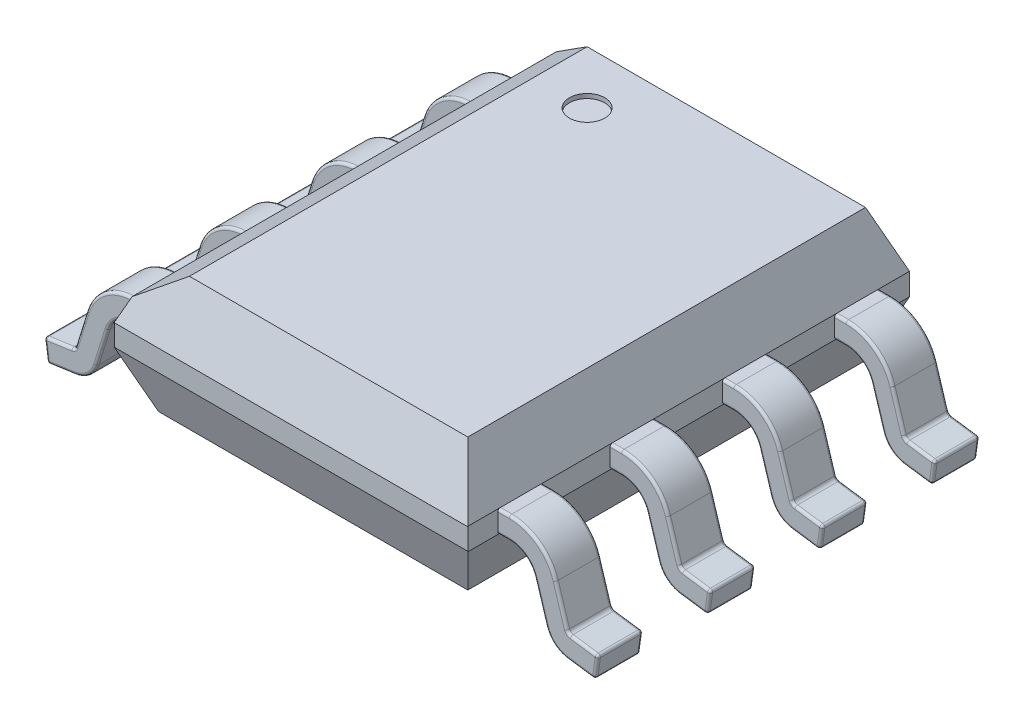
SolidWorks part; units mm, degrees
ref_plane "Front" through (0, 0, 0) normal (0, 0, 1) x (1, 0, 0)
ref_plane "Top" through (0, 0, 0) normal (0, 1, 0) x (1, 0, 0)
ref_plane "Right" through (0, 0, 0) normal (1, 0, 0) x (0, 0, -1)
sketch "Эскиз1" plane through (0, 0, 0) normal (0, 0, 1) x (1, 0, 0)
  line L0 (-1.75, 0.25) -> (1.75, 0.25)
  line L1 (1.75, 0.25) -> (2, 0.875)
  line L2 (2, 0.875) -> (2, 1.125)
  line L3 (2, 1.125) -> (1.75, 1.75)
  line L4 (1.75, 1.75) -> (-1.4, 1.75)
  line L5 (-1.4, 1.75) -> (-1.9, 1.375)
  line L6 (-1.9, 1.375) -> (-2, 1.125)
  line L7 (-2, 1.125) -> (-2, 0.875)
  line L8 (-2, 0.875) -> (-1.75, 0.25)
  line L9 (0, 0.25) -> (0, 1.75) construction
  line L10 (-2, 0.875) -> (-2.1291, 0.875)
  line L11 (-2.4155, 0.664) -> (-2.5436, 0.2519)
  line L12 (-2.7883, 0.0438) -> (-3.1, 0)
  line L13 (-2, 1.125) -> (-2.1291, 1.125)
  line L14 (-2.6543, 0.7382) -> (-2.7823, 0.3261)
  line L15 (-2.8231, 0.2914) -> (-3.1348, 0.2476)
  line L16 (-3.1, 0) -> (-3.1348, 0.2476)
  line L17 (-3.1, 0) -> (0, 0) construction
  line L18 (-2, 1) -> (2, 1) construction
  arc A0 (-2.7883, 0.0438) -> (-2.5436, 0.2519) centre (-2.8301, 0.3409) ccw
  arc A1 (-2.4155, 0.664) -> (-2.1291, 0.875) centre (-2.1291, 0.575) cw
  arc A2 (-2.6543, 0.7382) -> (-2.1291, 1.125) centre (-2.1291, 0.575) cw
  arc A3 (-2.8231, 0.2914) -> (-2.7823, 0.3261) centre (-2.8301, 0.3409) ccw
  point P11 (0, 1)
  point P18 (-2.6, 0.0703)
  point P24 (-2.35, 0.875)
  dimension "D11" = 0.3
  dimension "D1" = 1.5
  dimension "D2" = 0.25
  dimension "D3" = 4
  dimension "D4" = 0.25
  dimension "D5" = 0.25
  dimension "D6" = 0.5
  dimension "D7" = 0.25
  dimension "D8" = 3.1
  dimension "D9" = 8
  dimension "D10" = 0.5
  dimension "D12" = 0.25
  dimension "D13" = 0.25
  dimension "D14" = 0.625
extrude "Бобышка-Вытянуть1" add sketch "Эскиз1" along normal blind 2.5 and the other way blind 2.5 contours L7 L8 L0 L1 L2 L3 L4 L5 L6 region at (0.0196, 0.9927, 0)
extrude "Бобышка-Вытянуть2" add sketch "Эскиз1<3>" along normal blind 0.255 and the other way blind 0.255 from offset 1.905 separate body contours A3 L15 L16 L12 A0 L11 A1 L10 L7 L13 A2 L14 region at (-2.5637, 0.567, 0)
sketch "Эскиз1<3>" plane through (0, 0, 0) normal (0, 0, 1) x (1, 0, 0) same geometry as "Эскиз1"
fillet "Скругление1" radius 0.03 24 edges at (-2.0645, 0.875, 1.65) (-2.307, 0.8166, 1.65) (-2.4796, 0.4579, 1.65) (-2.6358, 0.1123, 1.65) (-2.0645, 0.875, 2.16) (-2.307, 0.8166, 2.16) (-2.4796, 0.4579, 2.16) (-2.6358, 0.1123, 2.16) (-2.7183, 0.5321, 1.65) (-2.0645, 1.125, 1.65) (-2.7183, 0.5321, 2.16) (-2.0645, 1.125, 2.16) (-3.1174, 0.1238, 1.65) (-3.1, 0, 1.905) (-3.1174, 0.1238, 2.16) (-3.1348, 0.2476, 1.905) (-2.9442, 0.0219, 1.65) (-2.979, 0.2695, 1.65) (-2.979, 0.2695, 2.16) (-2.9442, 0.0219, 2.16) (-2.7977, 0.3028, 1.65) (-2.4552, 1.0179, 1.65) (-2.7977, 0.3028, 2.16) (-2.4552, 1.0179, 2.16)
pattern_linear "Линейный массив1" count 4 spacing 1.27 along (0, 0, -1) of bodies 102
mirror "Зеркальное отражение1" about plane through (0, 0, 0) normal (1, 0, 0) of bodies 102 103 104 105
chamfer "Фаска1" distance 0.25 distance2 0.63 2 edges at (0, 0.25, 2.5) (0.175, 1.75, 2.5) first distance on face at (0, 0.25, 0) first distance on face at (0.175, 1.75, 0)
chamfer "Фаска2" distance 0.63 distance2 0.25 2 edges at (0, 0.25, -2.5) (0.175, 1.75, -2.5) first distance on face at (-0.1722, 1.0417, -2.5)
sketch "Эскиз2" plane through (0, 1.75, 0) normal (0, 1, 0) x (1, 0, 0)
  line L0 (-1.4, 2.25) -> (-1.4, -2.25) construction
  line L1 (1.75, 2.25) -> (-1.4, 2.25) construction
  circle A0 centre (-0.8, 1.65) radius 0.2
  dimension "D1" = 0.4
  dimension "D2" = 0.6
  dimension "D3" = 0.6
extrude "Вырез-Вытянуть1" cut sketch "Эскиз2" against normal blind 0.05
